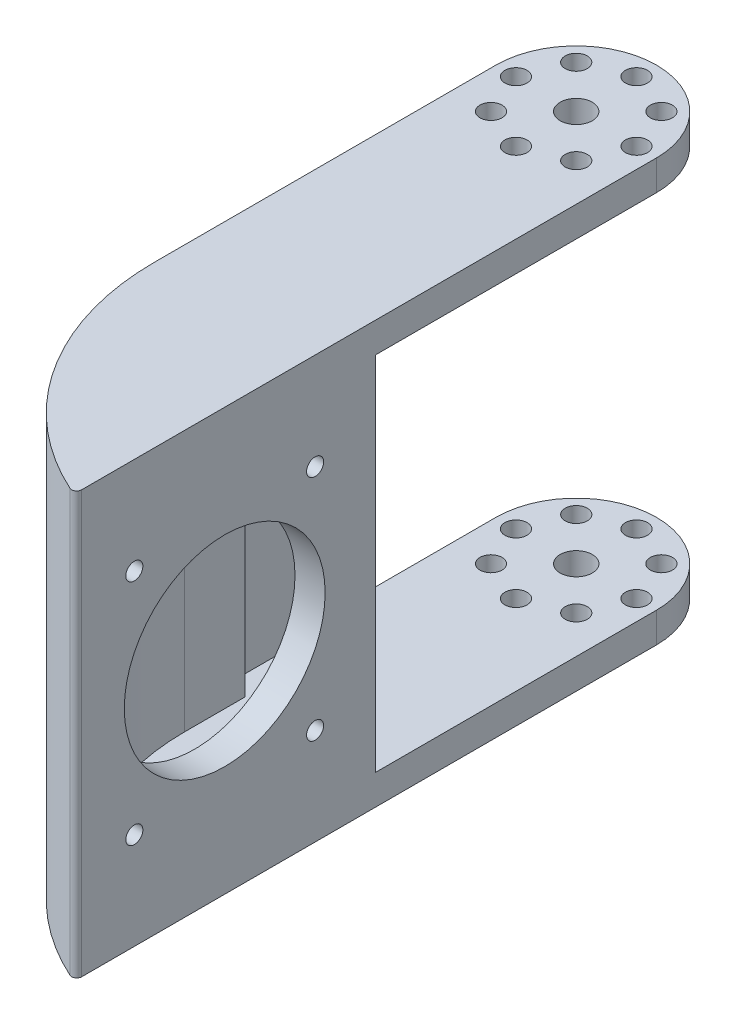
SolidWorks part; units mm, degrees
material "ABS"
ref_plane "正面" through (0, 0, 0) normal (0, 0, 1) x (1, 0, 0)
ref_plane "平面" through (0, 0, 0) normal (0, 1, 0) x (1, 0, 0)
ref_plane "右側面" through (0, 0, 0) normal (1, 0, 0) x (0, 0, -1)
sketch "ｽｹｯﾁ1" plane through (0, 0, 0) normal (0, 1, 0) x (1, 0, 0)
  line L0 (-8, 45) -> (-8, -13)
  line L7 (-8, -13) -> (8, -13)
  line L8 (8, -13) -> (8, 45)
  arc A4 (8, 45) -> (-8, 45) centre (0, 45) ccw
  circle A5 centre (0, 45) radius 6 construction
  circle A6 centre (0, 51) radius 1.1
  circle A7 centre (4.2426, 49.2426) radius 1.1
  circle A8 centre (6, 45) radius 1.1
  circle A9 centre (4.2426, 40.7574) radius 1.1
  circle A10 centre (0, 39) radius 1.1
  circle A11 centre (-4.2426, 40.7574) radius 1.1
  circle A12 centre (-6, 45) radius 1.1
  circle A13 centre (-4.2426, 49.2426) radius 1.1
  circle A14 centre (0, 45) radius 1.6
  point P0 (0, 0)
  point P35 (0, 45)
  dimension "D9" = 45
  dimension "D10" = 12
  dimension "D11" = 2.2
  dimension "D13" = 3.2
  dimension "D6" = 8
  dimension "D7" = 8
  dimension "D8" = 13
  dimension "D12" = 8
extrude "ﾎﾞｽ - 押し出し1" add sketch "ｽｹｯﾁ1" along normal blind 3
ref_plane "平面1" through (0, -36, 0) normal (0, 1, 0) x (1, 0, 0)
sketch "ｽｹｯﾁ2" plane through (0, -36, 0) normal (0, 1, 0) x (1, 0, 0)
  line L3 (8, -13) -> (8, 45)
  line L4 (-8, -13) -> (8, -13)
  line L5 (-8, 45) -> (-8, -13)
  line L6 (8, -13) -> (8, 45)
  line L7 (-8, -13) -> (8, -13)
  line L8 (-8, 45) -> (-8, -13)
  circle A0 centre (0, 45) radius 1.6
  arc A1 (8, 45) -> (-8, 45) centre (0, 45) ccw
  arc A2 (8, 45) -> (-8, 45) centre (0, 45) ccw
  circle A3 centre (0, 45) radius 6 construction
  circle A4 centre (0, 51) radius 1.1
  circle A5 centre (4.2426, 49.2426) radius 1.1
  circle A6 centre (6, 45) radius 1.1
  circle A7 centre (4.2426, 40.7574) radius 1.1
  circle A8 centre (0, 39) radius 1.1
  circle A9 centre (-4.2426, 40.7574) radius 1.1
  circle A10 centre (-6, 45) radius 1.1
  circle A11 centre (-4.2426, 49.2426) radius 1.1
  point P25 (0, 45)
  dimension "D2" = 3.2
  dimension "D3" = 12
  dimension "D4" = 2.2
  dimension "D1" = 0
  dimension "D5" = 8
extrude "ﾎﾞｽ - 押し出し2" add sketch "ｽｹｯﾁ2" against normal blind 3 separate body
sketch "ｽｹｯﾁ3" plane through (0, 0, 13) normal (0, 0, 1) x (1, 0, 0)
  line L1 (-8, -36) -> (8, -36)
  line L2 (-8, -36) -> (-8, 0)
  line L3 (-8, 0) -> (8, 0)
  line L4 (8, -36) -> (8, 0)
extrude "ﾎﾞｽ - 押し出し3" add sketch "ｽｹｯﾁ3" against normal blind 30
fillet "ﾌｨﾚｯﾄ1" radius 26 1 edges at (-8, -18, 13)
sketch "ｽｹｯﾁ5" plane through (-8, 0, 0) normal (-1, 0, 0) x (0, 0, 1)
  line L1 (-17, 0) -> (-27, 0)
  line L2 (-17, 0) -> (-17, -36)
  line L3 (-17, -36) -> (-27, -36)
  line L4 (-27, 0) -> (-27, -36)
  line L5 (-45, -36) -> (-17, -36) construction
  dimension "D1" = 10
extrude "ﾎﾞｽ - 押し出し4" add sketch "ｽｹｯﾁ5" against normal blind 1
sketch "ｽｹｯﾁ7" plane through (0, 0, 0) normal (0, -1, 0) x (1, 0, 0)
  line L0 (5, 7.9737) -> (5, -17)
  line L1 (8, -17) -> (-7, -17) construction
  line L2 (5, -17) -> (-5, -17)
  line L3 (-5, -17) -> (-5, -11)
  line L4 (8, -17) -> (8, -45) construction
  arc A0 (9.1538, 10.2308) -> (-5, -11) centre (18, -11) ccw construction
  arc A2 (8, 13) -> (-8, -11) centre (18, -11) ccw
  arc A3 (8, 13) -> (-8, -11) centre (18, -11) ccw construction
  arc A4 (5, 7.9737) -> (-5, -11) centre (18, -11) ccw
  dimension "D2" = 3
  dimension "D1" = 3
extrude "ｶｯﾄ - 押し出し2" cut sketch "ｽｹｯﾁ7" along normal up to surface (36 mm away) up to face at (-2.3333, -36, -31)
sketch "ｽｹｯﾁ6" plane through (8, 0, 0) normal (1, 0, 0) x (0, 0, -1)
  line L0 (2, 3) -> (2, -39) construction
  line L1 (-13, 3) -> (45, 3) construction
  line L2 (-13, 3) -> (-13, -39) construction
  line L3 (-13, -39) -> (45, -39) construction
  circle A0 centre (2, -18) radius 15 construction
  circle A1 centre (2, -18) radius 20 construction
  circle A2 centre (2, -18) radius 14.5 construction
  circle A3 centre (11, -6.6312) radius 0.85
  circle A4 centre (-7, -6.6312) radius 0.85
  circle A5 centre (-7, -29.3688) radius 0.85
  circle A6 centre (11, -29.3688) radius 0.85
  circle A7 centre (2, -18) radius 10
  dimension "D1" = 30
  dimension "D2" = 40
  dimension "D4" = 29
  dimension "D5" = 1.7
  dimension "D7" = 20
  dimension "D3" = 15
  dimension "D6" = 9
extrude "ｶｯﾄ - 押し出し1" cut sketch "ｽｹｯﾁ6" against normal up to surface (3 mm away) up to face at (5, -18, -4.5132)
fillet "ﾌｨﾚｯﾄ2" radius 0.5 1 edges at (8, -18, 13)
